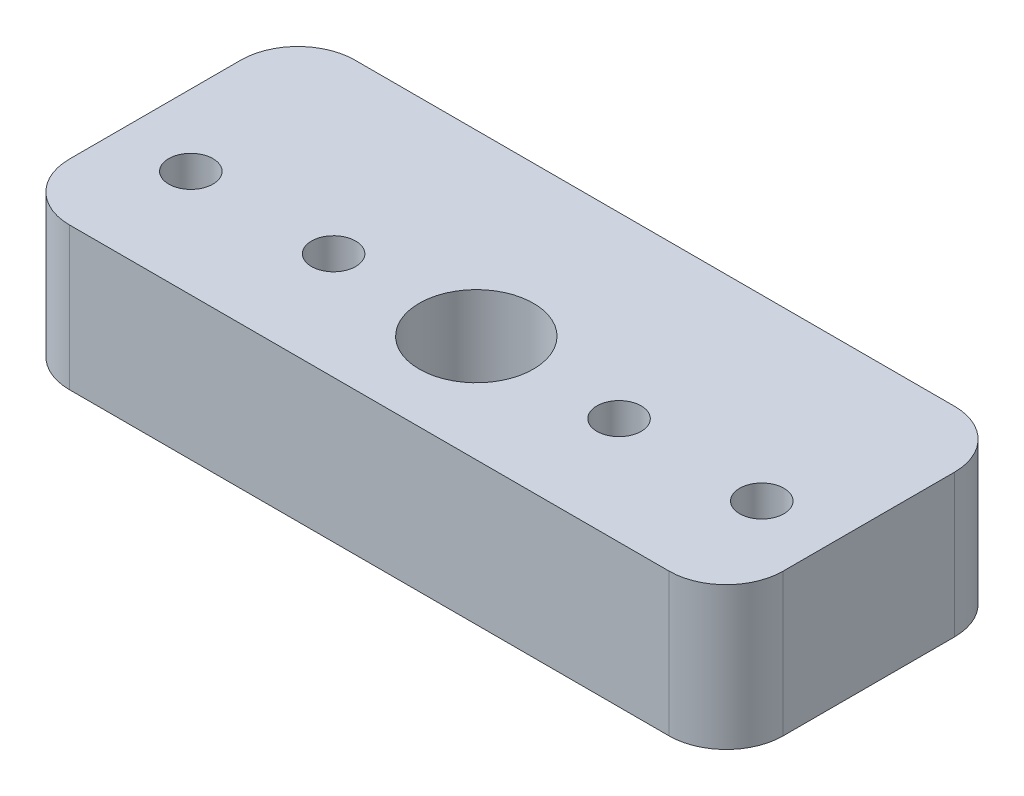
SolidWorks part; units mm, degrees
ref_plane "Front Plane" through (0, 0, 0) normal (0, 0, 1) x (1, 0, 0)
ref_plane "Top Plane" through (0, 0, 0) normal (0, 1, 0) x (1, 0, 0)
ref_plane "Right Plane" through (0, 0, 0) normal (1, 0, 0) x (0, 0, -1)
sketch "Sketch1" plane through (0, 0, 0) normal (0, 1, 0) x (1, 0, 0)
  line L0 (-25, -2.5) -> (25, -2.5) construction
  line L1 (-21, 10) -> (21, 10)
  line L2 (-25, 6) -> (-25, -6)
  line L3 (-21, -10) -> (21, -10)
  line L4 (25, 6) -> (25, -6)
  line L5 (-25, 10) -> (25, -10) construction
  line L6 (-25, -10) -> (25, 10) construction
  line L7 (0, -10) -> (0, 10) construction
  line L8 (25, 10) -> (-25, -10) construction
  arc A0 (-25, -6) -> (-21, -10) centre (-21, -6) ccw
  arc A1 (21, -10) -> (25, -6) centre (21, -6) ccw
  arc A2 (21, 10) -> (25, 6) centre (21, 6) cw
  arc A3 (-21, 10) -> (-25, 6) centre (-21, 6) ccw
  circle A4 centre (0, -2.5) radius 4
  circle A5 centre (10, -2.5) radius 1.55
  circle A6 centre (20, -2.5) radius 1.55
  circle A7 centre (-20, -2.5) radius 1.55
  circle A8 centre (-10, -2.5) radius 1.55
  point P0 (0, 0)
  dimension "D3" = 4
  dimension "D4" = 8
  dimension "D5" = 3.1
  dimension "D6" = 3.1
  dimension "D1" = 20
  dimension "D7" = 7.5
  dimension "D8" = 10
  dimension "D9" = 40
  dimension "D2" = 5
extrude "Boss-Extrude1" add sketch "Sketch1" along normal blind 10
equation "\"Y-ROD-SPACING\"=75"
equation "\"Y-BED-OFFSET\"=2"
equation "\"Y-BED-ROD-INSET\"=3.5"
equation "\"T-SLOT-NUT-FILLET-RADIUS\"=0.25"
equation "\"T-SLOT-SCREW-SHAFT-RADIUS\"=1.75"
equation "\"T-SLOT-SCREW-SHAFT-CUTOUT-LENGTH\"=10.5"
equation "\"T-SLOT-NUT-DEPTH\"=4.2"
equation "\"T-SLOT-NUT-WIDTH\"=3"
equation "\"T-SLOT-NUT-END-DISTANCE\"=8"
equation "\"ACRYLIC-TAB-CUTOUT-SIZE\"=\"ACRYLIC-THICKNESS\"+\"ACRYLIC-TAB-TOLERANCE\"*2"
equation "\"ACRYLIC-M3-HOLE\"=3.1"
equation "\"SMOOTHROD-CAP-SCREW-DISTANCE\"=20"
equation "\"D5@Sketch1\"=\"ACRYLIC-M3-HOLE\""
equation "\"D6@Sketch1\"=\"ACRYLIC-M3-HOLE\""
equation "\"D8@Sketch1\"=\"SMOOTHROD-CAP-SCREW-DISTANCE\"/2"
equation "\"ACRYLIC-TAB-WIDTH\"=\"ACRYLIC-THICKNESS\""
equation "\"FRAME-WIDTH-INNER\"=370"
equation "\"NEMA17-HOLE-SPACING\"=31"
equation "\"NEMA17-CENTRAL-CUTOUT\"=22.5"
equation "\"Z-BRACKET-REACH\"=55"
equation "\"TOP-BRACKET-SPACING\"=40"
equation "\"D9@Sketch1\"=\"TOP-BRACKET-SPACING\""
equation "\"D2@Sketch1\"=\"ACRYLIC-TAB-WIDTH\"/2"
equation "\"X-ROD-SPACING\"=45"
equation "\"Z-ROD-SPACING\"=17.5"
equation "\"ACRYLIC-THICKNESS\"=10"
equation "\"ACRYLIC-THICKNESS2\"=4.5"
equation "\"SMOOTHROD-X-LENGTH\"=350"
equation "\"SMOOTHROD-Y-LENGTH\"=350"
equation "\"SMOOTHROD-Z-LENGTH\"=350"
equation "\"SMOOTHROD-TIGHTENING-HEADROOM\"=.25"
equation "\"LEADSCREW-Z-LENGTH\"=300"
equation "\"SCREW-LENGTH-FRAME\"=\"ACRYLIC-THICKNESS\" + 10"
equation "\"SCREW-HEAD-RADIUS\"=6"
equation "\"PRINTED-X-SMOOTHROD-DIAMETER\"=8.2"
equation "\"PRINTED-X-SMOOTHROD-CUTOUT\"=10"
equation "\"PRINTED-X-BASE-HEIGHT\"=10"
equation "\"PRINTED-LM8UU-CUTOUT-SIZE\"=15.25"
equation "\"PRINTED-LM8UU-CUTOUT-LENGTH\"=24.5"
equation "\"PRINTED-X-IDLER-HEIGHT\"=16"
equation "\"PSU-MOUNTING-WIDTH\"=95"
equation "\"PSU-MOUNTING-HEIGHT\"=177"
equation "\"D1@Boss-Extrude1\"=\"ACRYLIC-THICKNESS\""
